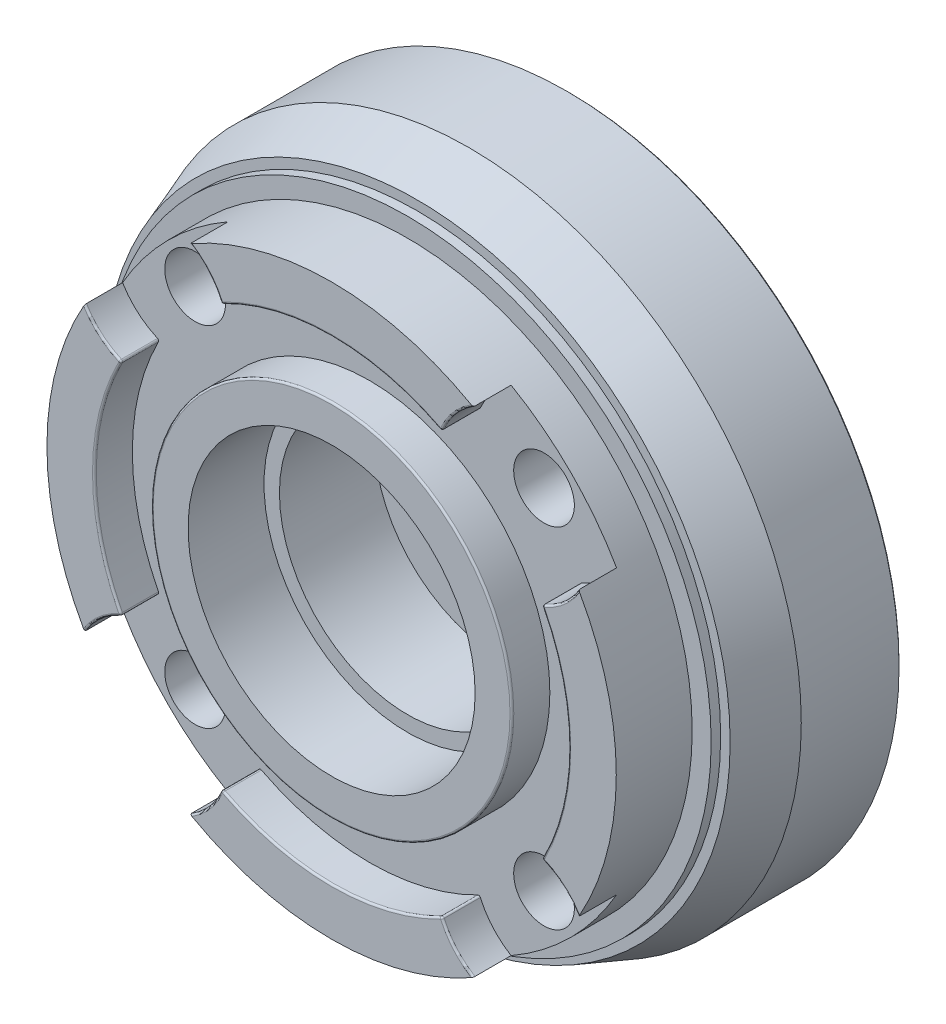
SolidWorks part; units mm, degrees
material "ABS"
ref_plane "Front Plane" through (0, 0, 0) normal (0, 0, 1) x (1, 0, 0)
ref_plane "Top Plane" through (0, 0, 0) normal (0, 1, 0) x (1, 0, 0)
ref_plane "Right Plane" through (0, 0, 0) normal (1, 0, 0) x (0, 0, -1)
sketch "Sketch1" plane through (0, 0, 0) normal (0, 0, 1) x (1, 0, 0)
  line L0 (0, 0) -> (13.5, 0) construction
  line L1 (0, 0) -> (9.5459, 9.5459) construction
  circle A0 centre (0, 0) radius 9.5
  circle A1 centre (0, 0) radius 15
  arc A2 (-6.285, 11.9478) -> (-11.9478, 6.285) centre (0, 0) ccw construction
  arc A3 (7.4565, 13.0154) -> (5.7957, 11.0752) centre (9.5459, 9.5459) ccw
  arc A4 (13.0154, -7.4565) -> (11.0752, -5.7957) centre (9.5459, -9.5459) ccw
  arc A5 (-7.4565, -13.0154) -> (-5.7957, -11.0752) centre (-9.5459, -9.5459) ccw
  arc A6 (-13.0154, 7.4565) -> (-11.0752, 5.7957) centre (-9.5459, 9.5459) ccw
  arc A7 (-11.0752, 5.7957) -> (-11.0752, -5.7957) centre (0, 0) ccw
  arc A8 (11.9478, 6.285) -> (6.285, 11.9478) centre (0, 0) ccw construction
  arc A9 (6.285, -11.9478) -> (11.9478, -6.285) centre (0, 0) ccw construction
  arc A10 (-11.9478, -6.285) -> (-6.285, -11.9478) centre (0, 0) ccw construction
  arc A11 (5.7957, 11.0752) -> (-5.7957, 11.0752) centre (0, 0) ccw
  arc A12 (-5.7957, -11.0752) -> (5.7957, -11.0752) centre (0, 0) ccw
  arc A13 (11.0752, -5.7957) -> (11.0752, 5.7957) centre (0, 0) ccw
  arc A14 (-5.7957, 11.0752) -> (-7.4565, 13.0154) centre (-9.5459, 9.5459) ccw
  arc A15 (11.0752, 5.7957) -> (13.0154, 7.4565) centre (9.5459, 9.5459) ccw
  arc A16 (5.7957, -11.0752) -> (7.4565, -13.0154) centre (9.5459, -9.5459) ccw
  arc A17 (-11.0752, -5.7957) -> (-13.0154, -7.4565) centre (-9.5459, -9.5459) ccw
  circle A18 centre (0, 0) radius 7.5625
  point P17 (0, 0)
  dimension "D1" = 19
  dimension "D2" = 30
  dimension "D3" = 27
  dimension "D4" = 45
  dimension "D5" = 8.1
  dimension "D6" = 4
  dimension "D7" = 25
  dimension "D8" = 15.125
extrude "Boss-Extrude1" add sketch "Sketch1" along normal blind 2 contours A14 A11 A3 A1 | A15 A13 A4 A1 | A16 A12 A5 A1 | A17 A7 A6 A1 | A0 A18 region at (-9.2313, 0, 0) region at (13.2504, 0, 0) region at (0, 13.2504, 0) region at (0, -13.2504, 0) region at (-13.2504, 0, 0)
sketch "Sketch2" plane through (0, 0, 0) normal (0, 0, 1) x (1, 0, 0)
  circle A0 centre (0, 0) radius 15
extrude "Boss-Extrude2" add sketch "Sketch2" against normal blind 2
fillet "Fillet1" radius 0.1 8 edges at (-5.7957, -11.0752, 1) (5.7957, -11.0752, 1) (11.0752, -5.7957, 1) (11.0752, 5.7957, 1) (5.7957, 11.0752, 1) (-5.7957, 11.0752, 1) (-11.0752, 5.7957, 1) (-11.0752, -5.7957, 1)
fillet "Fillet2" radius 0.1 21 edges at (6.5042, 12.2199, 2) (5.7793, 11.1194, 2) (-6.5042, 12.2199, 2) (-5.7793, 11.1194, 2) (12.2199, -6.5042, 2) (11.1194, -5.7793, 2) (12.2199, 6.5042, 2) (11.1194, 5.7793, 2) (-6.5042, -12.2199, 2) (-5.7793, -11.1194, 2) (6.5042, -12.2199, 2) (5.7793, -11.1194, 2) (-12.2199, 6.5042, 2) (-11.1194, 5.7793, 2) (-12.2199, -6.5042, 2) (-11.1194, -5.7793, 2) (0, 12.5, 2) (12.5, 0, 2) (0, -12.5, 2) (9.5, 0, 2) (-12.5, 0, 2)
sketch "Sketch3" plane through (0, 0, -2) normal (0, 0, -1) x (-1, 0, 0)
  line L1 (9.1924, 9.1924) -> (-9.1924, 9.1924) construction
  line L2 (-9.1924, 9.1924) -> (-9.1924, -9.1924) construction
  line L3 (-9.1924, -9.1924) -> (9.1924, -9.1924) construction
  line L4 (9.1924, -9.1924) -> (9.1924, 9.1924) construction
  circle A0 centre (0, 0) radius 13 construction
  circle A1 centre (-9.1924, 9.1924) radius 1.6
  circle A2 centre (9.1924, 9.1924) radius 1.6
  circle A3 centre (9.1924, -9.1924) radius 1.6
  circle A4 centre (-9.1924, -9.1924) radius 1.6
  point P17 (0, 0)
  dimension "D1" = 26
  dimension "D2" = 3.2
  dimension "D3" = 4
sketch "Sketch4" plane through (0, 0, -2) normal (0, 0, -1) x (-1, 0, 0)
  circle A0 centre (0, 0) radius 16
  dimension "D1" = 32
extrude "Boss-Extrude3" add sketch "Sketch4" along normal blind 0.5
sketch "Sketch5" plane through (0, 0, -2.5) normal (0, 0, -1) x (-1, 0, 0)
  circle A0 centre (0, 0) radius 17.5
  dimension "D1" = 35
extrude "Boss-Extrude4" add sketch "Sketch5" along normal blind 8
extrude "Cut-Extrude2" cut sketch "Sketch3" against normal through all and the other way through all
sketch "Sketch6" plane through (0, 0, -10.5) normal (0, 0, -1) x (-1, 0, 0)
  circle A0 centre (-9.1924, 9.1924) radius 2.1
  circle A1 centre (9.1924, 9.1924) radius 2.1
  circle A2 centre (9.1924, -9.1924) radius 2.1
  circle A3 centre (-9.1924, -9.1924) radius 2.1
  point P12 (0, 0)
  dimension "D1" = 4.2
  dimension "D2" = 4
extrude "Cut-Extrude3" cut sketch "Sketch6" against normal blind 8
sketch "Sketch7" plane through (0, 0, -10.5) normal (0, 0, -1) x (-1, 0, 0)
  line L0 (0, 0) -> (0, 13) construction
  line L1 (0, 13) -> (-13, 0) construction
  line L2 (-13, 0) -> (0, -13) construction
  line L3 (0, -13) -> (13, 0) construction
  line L4 (13, 0) -> (0, 13) construction
  circle A0 centre (0, 0) radius 13 construction
  circle A1 centre (0, 13) radius 2.6
  circle A2 centre (13, 0) radius 2.6
  circle A3 centre (0, -13) radius 2.6
  circle A4 centre (-13, 0) radius 2.6
  point P17 (0, 0)
  dimension "D1" = 26
  dimension "D2" = 5.2
  dimension "D3" = 4
extrude "Cut-Extrude4" cut sketch "Sketch7" against normal blind 8
sketch "Sketch8" plane through (0, 0, 0) normal (0, 0, 1) x (1, 0, 0)
  circle A0 centre (0, 0) radius 6.75
  dimension "D1" = 13.5
extrude "Middle Cutout" cut sketch "Sketch8" against normal blind 7
chamfer "Chamfer1" distance 0.1 angle 45 1 edges at (-17.5, 0, -10.5)
sketch "Sketch9" plane through (0, 0, 0) normal (0, 0, 1) x (1, 0, 0)
  circle A0 centre (0, 0) radius 7.5625
  dimension "D1" = 15.125
extrude "Cut-Extrude6" cut sketch "Sketch9" against normal blind 2
chamfer "Chamfer2" distance 1 angle 70 1 edges at (-17.5, 0, -2.5) first distance on face at (-16, 0, -2.5)
equation "\"RingPinShaft\"= 5.05"
equation "\"CenterBearingOut\"=32.05"
equation "\"OutputBearingOut\"=37.05"
equation "\"RingPostIn\"=5.15"
equation "\"CamBearingOut\"=15.1"
equation "\"DiskOutputShaft\"=10.1"
equation "\"CenterShaft\"=25.2"
equation "\"Eccentricity\"=2"
equation "\"CycCamShaft\"=10.05"
equation "\"m3Thru\"=3.15"
equation "\"m3Insert\"=4.2"
equation "\"D1@Sketch6\"=\"m3Insert\""
